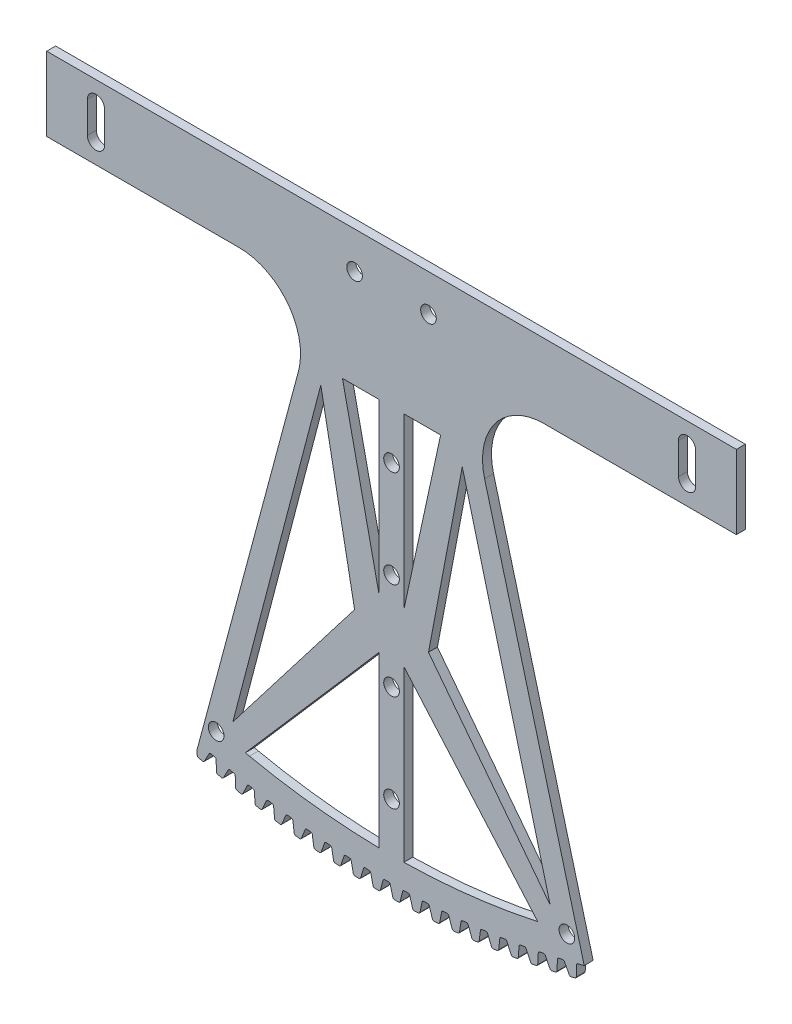
SolidWorks part; units mm, degrees
material "Maple"
ref_plane "Front Plane" through (0, 0, 0) normal (0, 0, 1) x (1, 0, 0)
ref_plane "Top Plane" through (0, 0, 0) normal (0, 1, 0) x (1, 0, 0)
ref_plane "Right Plane" through (0, 0, 0) normal (1, 0, 0) x (0, 0, -1)
sketch "Sketch3" plane through (0, 0, 0) normal (0, 0, 1) x (1, 0, 0)
  line L0 (0, 0) -> (0, -304.8) construction
  line L1 (-21.234, -79.2464) -> (-78.888, -294.4142)
  line L2 (21.234, -79.2464) -> (78.888, -294.4142)
  line L4 (-140, -79.56) -> (140, -79.56)
  line L5 (-140, -79.56) -> (-140, -109.56)
  line L6 (-140, -109.56) -> (140, -109.56)
  line L7 (140, -79.56) -> (140, -109.56)
  line L8 (0, -109.56) -> (0, -79.56) construction
  line L9 (-140, -94.56) -> (140, -94.56) construction
  arc A0 (-78.888, -294.4142) -> (78.888, -294.4142) centre (0, 0) ccw
  point P269 (0, -94.56)
  dimension "D1" = 304.8
  dimension "D4" = 79.56
  dimension "D5" = 30
  dimension "D6" = 280
  dimension "D7" = 140
extrude "Boss-Extrude2" add sketch "Sketch3" along normal blind 3.6286 contours L7 L4 L2 L6 | L1 L6 L2 L4 | L1 L4 L2 | L5 L6 L1 L4 | L1 A0 L2 L6 region at (0, -95.3531, 0) region at (-82.6452, -94.3847, 0) region at (0, -220.3694, 0) region at (82.6452, -94.3847, 0)
fillet "Fillet1" radius 25 2 edges at (-29.3565, -109.56, 1.8143) (29.3565, -109.56, 1.8143)
sketch "Sketch4" plane through (0, -79.56, 0) normal (0, 1, 0) x (1, 0, 0)
  line L1 (-140, 0) -> (140, 0)
  line L2 (-140, 0) -> (-140, -3.6286)
  line L3 (-140, -3.6286) -> (140, -3.6286)
  line L4 (140, 0) -> (140, -3.6286)
  line L5 (0, -3.6286) -> (0, 0) construction
  line L6 (-140, -1.8143) -> (140, -1.8143) construction
  point P252 (0, -1.8143)
sketch "Sketch5" plane through (0, 0, 0) normal (0, 0, -1) x (-1, 0, 0)
  line L0 (-123.5, -94.56) -> (-123.5, -100.91)
  line L1 (-116.5, -94.56) -> (-116.5, -100.91)
  line L2 (116.5, -94.56) -> (116.5, -88.21)
  line L3 (140, -79.56) -> (-140, -79.56) construction
  line L4 (-120, -88.21) -> (-120, -100.91) construction
  line L5 (0, -79.56) -> (0, -109.56) construction
  line L6 (-116.5, -94.56) -> (-116.5, -88.21)
  line L7 (-123.5, -94.56) -> (-123.5, -88.21)
  line L8 (116.5, -94.56) -> (116.5, -100.91)
  line L9 (123.5, -94.56) -> (123.5, -100.91)
  line L10 (123.5, -94.56) -> (123.5, -88.21)
  line L11 (-140, -79.56) -> (-140, -109.56) construction
  line L12 (120, -88.21) -> (120, -100.91) construction
  arc A1 (-116.5, -88.21) -> (-123.5, -88.21) centre (-120, -88.21) ccw
  arc A2 (-123.5, -100.91) -> (-116.5, -100.91) centre (-120, -100.91) ccw
  arc A3 (123.5, -100.91) -> (116.5, -100.91) centre (120, -100.91) cw
  arc A4 (116.5, -88.21) -> (123.5, -88.21) centre (120, -88.21) cw
  circle A5 centre (-15, -94.56) radius 3.175
  circle A6 centre (15, -94.56) radius 3.175
  dimension "D1" = 16.5
  dimension "D2" = 7
  dimension "D3" = 8.65
  dimension "D5" = 3.5
  dimension "D6" = 15
  dimension "D8" = 6.35
  dimension "D4" = 6.35
  dimension "D7" = 15
sketch "Sketch13" plane through (0, 0, 0) normal (0, 0, -1) x (-1, 0, 0)
  line L0 (0, 0) -> (78.888, -294.4142)
  line L1 (0, 0) -> (-78.888, -294.4142)
  arc A0 (-78.888, -294.4142) -> (78.888, -294.4142) centre (0, 0) ccw
  arc A1 (-78.888, -294.4142) -> (78.888, -294.4142) centre (0, 0) ccw construction
  arc A2 (-78.888, -294.4142) -> (78.888, -294.4142) centre (0, 0) ccw
  circle A3 centre (0, 0) radius 304.8
  dimension "D1" = 609.6
sketch "Sketch14" plane through (0, 0, 0) normal (0, 0, -1) x (-1, 0, 0)
  line L0 (0, 0) -> (80.0203, -298.6399) construction
  line L2 (78.888, -294.4142) -> (78.9109, -297.0369)
  line L3 (78.9109, -297.0369) -> (76.2891, -297.7211)
  line L18 (76.2891, -297.7211) -> (75.0275, -295.4216)
  line L20 (0, 0) -> (-79.2746, -295.8555) construction
  line L32 (78.888, -294.4142) -> (75.0275, -295.4216)
  line L33 (75.0275, -295.4216) -> (78.888, -294.4142)
  line L34 (0, 0) -> (-75.3952, -296.8678) construction
  line L35 (0, 0) -> (-71.5028, -297.8293) construction
  line L36 (0, 0) -> (-67.5982, -298.7397) construction
  line L37 (0, 0) -> (-63.6821, -299.5989) construction
  line L38 (0, 0) -> (-59.755, -300.4068) construction
  line L39 (0, 0) -> (-55.8176, -301.1633) construction
  line L40 (0, 0) -> (-51.8707, -301.8681) construction
  line L41 (0, 0) -> (-47.9149, -302.5212) construction
  line L42 (0, 0) -> (-43.951, -303.1225) construction
  line L43 (0, 0) -> (-39.9794, -303.6718) construction
  line L44 (0, 0) -> (-36.0011, -304.1691) construction
  line L45 (0, 0) -> (-32.0165, -304.6143) construction
  line L46 (0, 0) -> (-28.0265, -305.0073) construction
  line L47 (0, 0) -> (-24.0316, -305.348) construction
  line L48 (0, 0) -> (-20.0327, -305.6364) construction
  line L49 (0, 0) -> (-16.0303, -305.8724) construction
  line L50 (0, 0) -> (-12.0252, -306.0561) construction
  line L51 (0, 0) -> (-8.018, -306.1873) construction
  line L52 (0, 0) -> (-4.0094, -306.266) construction
  line L53 (0, 0) -> (-0.0002, -306.2922) construction
  line L54 (0, 0) -> (4.0091, -306.266) construction
  line L55 (0, 0) -> (8.0176, -306.1873) construction
  line L56 (0, 0) -> (12.0248, -306.0561) construction
  line L57 (0, 0) -> (16.03, -305.8725) construction
  line L58 (0, 0) -> (20.0323, -305.6364) construction
  line L59 (0, 0) -> (24.0313, -305.348) construction
  line L60 (0, 0) -> (28.0261, -305.0073) construction
  line L61 (0, 0) -> (32.0162, -304.6143) construction
  line L62 (0, 0) -> (36.0007, -304.1691) construction
  line L63 (0, 0) -> (39.9791, -303.6719) construction
  line L64 (0, 0) -> (43.9506, -303.1225) construction
  line L65 (0, 0) -> (47.9146, -302.5213) construction
  line L66 (0, 0) -> (51.8704, -301.8682) construction
  line L67 (0, 0) -> (55.8173, -301.1633) construction
  line L68 (0, 0) -> (59.7546, -300.4069) construction
  line L69 (0, 0) -> (63.6817, -299.599) construction
  line L70 (0, 0) -> (67.5979, -298.7398) construction
  line L71 (0, 0) -> (71.5025, -297.8293) construction
  line L72 (0, 0) -> (75.3948, -296.8679) construction
  line L73 (0, 0) -> (-79.2746, -295.8555) construction
  line L74 (0, 0) -> (-75.3952, -296.8678) construction
  line L137 (37.789, -141.0305) -> (78.888, -294.4142) construction
  line L138 (-140, -79.56) -> (-140, -109.56)
  line L139 (-140, -109.56) -> (-61.9371, -109.56)
  line L140 (-37.789, -141.0305) -> (-78.888, -294.4142)
  line L141 (78.888, -294.4142) -> (37.789, -141.0305)
  line L142 (61.9371, -109.56) -> (140, -109.56)
  line L143 (140, -109.56) -> (140, -79.56)
  line L144 (140, -79.56) -> (-140, -79.56)
  line L145 (-140, -79.56) -> (-140, -109.56)
  line L146 (-140, -109.56) -> (-61.9371, -109.56)
  line L147 (-37.789, -141.0305) -> (-78.888, -294.4142)
  line L149 (61.9371, -109.56) -> (140, -109.56)
  line L150 (140, -109.56) -> (140, -79.56)
  line L151 (140, -79.56) -> (-140, -79.56)
  circle A0 centre (0, 0) radius 307.34
  circle A1 centre (0, 0) radius 302.26
  arc A3 (-37.789, -141.0305) -> (-61.9371, -109.56) centre (-61.9371, -134.56) ccw
  arc A5 (61.9371, -109.56) -> (37.789, -141.0305) centre (61.9371, -134.56) ccw
  arc A6 (-37.789, -141.0305) -> (-61.9371, -109.56) centre (-61.9371, -134.56) ccw
  arc A8 (61.9371, -109.56) -> (37.789, -141.0305) centre (61.9371, -134.56) ccw
  arc A11 (-78.888, -294.4142) -> (78.888, -294.4142) centre (0, 0) ccw
  arc A12 (-78.888, -294.4142) -> (78.888, -294.4142) centre (0, 0) ccw
  arc M181 (-78.888, -294.4142) -> (78.888, -294.4142) centre (0, 0) ccw
  dimension "D5" = 614.68
  dimension "D6" = 30
  dimension "D7" = 40
  dimension "D4" = 604.52
  dimension "D1" = 14.5
  dimension "D3" = 14.5
  dimension "D8" = 0.75
  dimension "D9" = 306.2922
  dimension "D10" = 0.75
  dimension "D2" = 0
extrude "Boss-Extrude4" add sketch "Sketch14" against normal up to surface (3.6286 mm away) contours L2 M181 region at (-77.2591, -296.0724, 0) up to face at (0, -146.6727, 3.6286)
sketch "Sketch15" plane through (0, 0, 0) normal (1, 0, 0) x (0, 0, -1)
  line L0 (0, 0) -> (-23.3364, 0) construction
sketch "Sketch16" plane through (0, 0, 0) normal (0, 0, -1) x (-1, 0, 0)
  line L0 (75.0275, -295.4216) -> (73.7653, -293.1208)
  line L1 (73.7653, -293.1208) -> (71.1999, -293.7544)
  line L2 (71.1999, -293.7544) -> (71.1541, -296.3784)
  line L3 (0, 0) -> (71.5025, -297.8293) construction
  line L4 (0, 0) -> (75.3948, -296.8679) construction
  circle A0 centre (0, 0) radius 302.26 construction
  arc A1 (-78.888, -294.4142) -> (78.888, -294.4142) centre (0, 0) ccw construction
  dimension "D1" = 14.5
  dimension "D2" = 14.5
extrude "Cut-Extrude2" cut sketch "Sketch16" against normal through all and the other way through all
fillet "Fillet2" radius 0.7 2 edges at (-76.2891, -297.7211, 1.8143) (-78.9109, -297.0369, 1.8143)
pattern_circular "CirPattern8" count 20 every 1.5 about axis through (0, 0, 0) along (0, 0, 1) of "Cut-Extrude2", "Boss-Extrude4", "Fillet2"
extrude "Cut-Extrude3" cut sketch "Sketch5" against normal through all
sketch "Sketch17" plane through (0, 0, 0) normal (0, 0, -1) x (-1, 0, 0)
  line L0 (0, -79.56) -> (0, -134.56) construction
  line L1 (140, -79.56) -> (-140, -79.56) construction
  line L2 (-61.9371, -109.56) -> (61.9371, -109.56) construction
  line L3 (-36.9371, -134.56) -> (-26.9371, -134.56) construction
  line L4 (-36.9371, -134.56) -> (-26.9371, -134.56) construction
  line L5 (-26.9371, -134.56) -> (-66.1944, -284.3612) construction
  line L6 (-66.1944, -284.3612) -> (-76.1944, -284.3612) construction
  line L7 (0, -292.2593) -> (5, -292.2593) construction
  line L8 (-37.789, -141.0305) -> (-78.888, -294.4142) construction
  line L9 (0, -134.56) -> (-5, -134.56) construction
  line L10 (0, -134.56) -> (5, -134.56) construction
  line L11 (26.9371, -134.56) -> (36.9371, -134.56) construction
  line L12 (-5, -134.56) -> (-5, -292.2593) construction
  line L13 (36.9371, -134.56) -> (26.9371, -134.56) construction
  line L14 (26.9371, -134.56) -> (66.1944, -284.3612) construction
  line L15 (66.1944, -284.3612) -> (76.1944, -284.3612) construction
  line L16 (37.789, -141.0305) -> (78.888, -294.4142) construction
  line L17 (0.6571, -302.2593) -> (-3.5916, -302.2593) construction
  line L18 (-5, -134.56) -> (5, -134.56) construction
  line L19 (-3.5916, -292.2593) -> (-5, -292.2593) construction
  line L20 (5, -134.56) -> (5, -292.2593) construction
  line L21 (-3.5916, -302.2593) -> (-3.5916, -292.2593) construction
  line L22 (0, -193.6972) -> (0, -233.1221) construction
  line L23 (64.4199, -277.5899) -> (15, -213.4096)
  line L24 (-66.1944, -284.3612) -> (-68.6354, -294.3612) construction
  line L25 (-67.3487, -294.6613) -> (-69.9221, -294.0612) construction
  line L26 (71.1999, -293.7544) -> (66.067, -294.9513) construction
  line L27 (66.1944, -284.3612) -> (68.6335, -294.3529) construction
  line L28 (26.9371, -134.56) -> (66.1944, -284.3612)
  line L29 (26.9371, -134.56) -> (5, -134.56)
  line L30 (5, -134.56) -> (5, -292.2593)
  line L31 (-66.1944, -284.3612) -> (-26.9371, -134.56)
  line L32 (-26.9371, -134.56) -> (-5, -134.56)
  line L33 (-5, -134.56) -> (-5, -292.2593)
  line L34 (15, -213.4096) -> (28.7117, -141.3313)
  line L35 (66.1944, -284.3612) -> (57.6779, -286.2946)
  line L36 (66.1944, -284.3612) -> (64.4199, -277.5899) construction
  line L37 (5, -223.4096) -> (59.3729, -285.9321)
  line L41 (26.9371, -134.56) -> (28.7117, -141.3313) construction
  line L42 (26.9371, -134.56) -> (19.9371, -134.56) construction
  line L44 (28.7117, -141.3313) -> (26.9371, -134.56) construction
  line L47 (5, -203.4096) -> (19.9371, -134.56)
  line L48 (-59.3729, -285.9321) -> (-5, -223.4096)
  line L50 (-64.4199, -277.5899) -> (-15, -213.4096)
  line L51 (-15, -213.4096) -> (-28.7117, -141.3313)
  line L52 (-5, -203.4096) -> (-19.9371, -134.56)
  circle A0 centre (0, -272.5469) radius 3.175
  arc A1 (61.9371, -109.56) -> (37.789, -141.0305) centre (61.9371, -134.56) ccw construction
  arc A2 (-37.789, -141.0305) -> (-61.9371, -109.56) centre (-61.9371, -134.56) ccw construction
  arc A3 (-66.1944, -284.3612) -> (-5, -292.2593) centre (0, -12.5018) ccw
  arc A4 (5, -292.2593) -> (66.1944, -284.3612) centre (0, -12.5018) ccw
  circle A5 centre (0, -233.1221) radius 3.175
  circle A6 centre (0, -193.6972) radius 3.175
  circle A7 centre (0, -154.2724) radius 3.175
  circle A8 centre (-71.1944, -284.3612) radius 3.175
  circle A9 centre (71.1944, -284.3612) radius 3.175
  arc A13 (19.9371, -134.56) -> (28.7117, -141.3313) centre (26.9371, -134.56) ccw construction
  arc A14 (19.9371, -134.56) -> (28.7117, -141.3313) centre (26.9371, -134.56) ccw construction
  arc A15 (-59.3729, -285.9321) -> (-64.4199, -277.5899) centre (-66.1944, -284.3612) ccw construction
  arc A16 (-64.4199, -277.5899) -> (-59.3729, -285.9321) centre (-66.1944, -284.3612) cw
  arc A17 (-5, -203.4096) -> (-5, -223.4096) centre (-5, -213.4096) ccw construction
  arc A18 (-28.7117, -141.3313) -> (-19.9371, -134.56) centre (-26.9371, -134.56) ccw construction
  arc A19 (5, -223.4096) -> (5, -203.4096) centre (5, -213.4096) ccw construction
  arc A20 (64.4199, -277.5899) -> (59.3729, -285.9321) centre (66.1944, -284.3612) ccw construction
  dimension "D13" = 6.35
  dimension "D14" = 6.35
  dimension "D15" = 10
  dimension "D16" = 7
  dimension "D17" = 7
  dimension "D20" = 7
  dimension "D21" = 10
  dimension "D22" = 7
  dimension "D18" = 7
  dimension "D1" = 10
  dimension "D2" = 5
  dimension "D3" = 10
  dimension "D4" = 10
  dimension "D5" = 5
  dimension "D6" = 5
  dimension "D7" = 10
  dimension "D8" = 10
  dimension "D9" = 5
  dimension "D10" = 10
  dimension "D11" = 157.6993
  dimension "D12" = 10
  dimension "D19" = 12.241
extrude "Cut-Extrude4" cut sketch "Sketch17" against normal through all contours L50 L51 L31 | L34 L23 L28 | L30 A4 L35 L37 | L48 A3 L33 | L30 L47 L29 | L52 L33 L32 | A6 | A7 | A5 | A0 | A9 | A8 region at (-36.0438, -210.777, 0) region at (-23.3567, -267.7722, 0) region at (-9.979, -157.5099, 0) region at (36.0438, -210.777, 0) region at (23.357, -267.7724, 0) region at (9.979, -157.5099, 0) region at (0, -272.5469, 0) region at (0, -233.1221, 0) region at (0, -193.6972, 0) region at (0, -154.2724, 0) region at (71.1944, -284.3612, 0) region at (-71.1944, -284.3612, 0)
fillet "Fillet3" radius 0.7 39 edges at (75.039, -292.7973, 1.8143) (69.9221, -294.0612, 1.8143) (67.3487, -294.6613, 1.8143) (62.2005, -295.7908, 1.8143) (59.6123, -296.3233, 1.8143) (54.4363, -297.3177, 1.8143) (51.835, -297.7822, 1.8143) (46.6348, -298.6408, 1.8143) (44.0223, -299.037, 1.8143) (38.8013, -299.7592, 1.8143) (36.1793, -300.0869, 1.8143) (30.9412, -300.6722, 1.8143) (28.3115, -300.9312, 1.8143) (23.06, -301.3791, 1.8143) (20.4244, -301.5692, 1.8143) (15.1629, -301.8794, 1.8143) (12.5232, -302.0005, 1.8143) (7.2554, -302.1729, 1.8143) (4.6135, -302.2248, 1.8143) (-3.2994, -302.242, 1.8143) (-0.6571, -302.2593, 1.8143) (-8.5691, -302.1385, 1.8143) (-11.2101, -302.0521, 1.8143) (-16.4752, -301.8107, 1.8143) (-19.113, -301.6551, 1.8143) (-24.37, -301.276, 1.8143) (-27.0029, -301.0514, 1.8143) (-32.2482, -300.5348, 1.8143) (-34.8743, -300.2414, 1.8143) (-40.1042, -299.5877, 1.8143) (-42.7217, -299.2256, 1.8143) (-47.9327, -298.4352, 1.8143) (-50.5399, -298.0047, 1.8143) (-55.7284, -297.0782, 1.8143) (-58.3234, -296.5796, 1.8143) (-63.4859, -295.5176, 1.8143) (-66.067, -294.9513, 1.8143) (-71.1999, -293.7544, 1.8143) (-73.7653, -293.1208, 1.8143)
sketch "Sketch18" plane through (0, 0, 3.6286) normal (0, 0, 1) x (1, 0, 0)
  line L0 (37.789, -141.0305) -> (78.8881, -294.4142) construction
  line L1 (78.2307, -291.9607) -> (79.419, -294.2998)
  line L2 (79.419, -294.2998) -> (78.2307, -294.9036)
  line L3 (78.2307, -294.9036) -> (77.5958, -292.1301)
  line L4 (77.5958, -292.1301) -> (78.2307, -291.9607)
  arc A0 (77.5958, -292.1301) -> (78.2307, -291.9607) centre (0, 0) cw
extrude "Cut-Extrude5" cut sketch "Sketch18" against normal blind 10 contours L4 L3 L2 L1 region at (78.4152, -293.4695, 3.6286)
equation "\"D7@Sketch3\"=\"D6@Sketch3\"/2"
